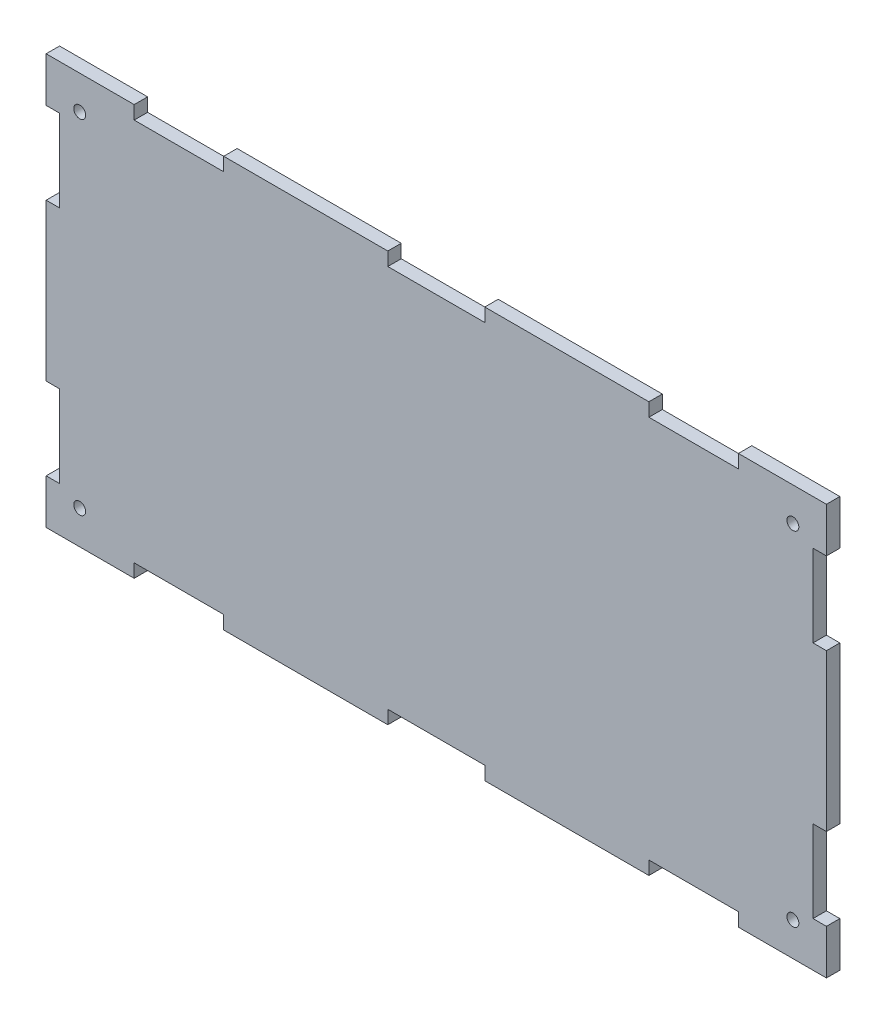
SolidWorks part; units mm, degrees
material "Бальса"
ref_plane "Спереди" through (0, 0, 0) normal (0, 0, 1) x (1, 0, 0)
ref_plane "Сверху" through (0, 0, 0) normal (0, 1, 0) x (1, 0, 0)
ref_plane "Справа" through (0, 0, 0) normal (1, 0, 0) x (0, 0, -1)
sketch "Эскиз1" plane through (0, 0, 0) normal (0, 0, 1) x (1, 0, 0)
  line L1 (0, 0) -> (209.2, 0)
  line L2 (0, 0) -> (0, 110)
  line L3 (0, 110) -> (209.2, 110)
  line L4 (209.2, 0) -> (209.2, 110)
  dimension "D1" = 110
  dimension "D2" = 209.2
base flange "Базовая кромка1" sketch "Эскиз1" thickness 3.6 reverse thickness direction no parameters "D1"=0.7366
sketch "Эскиз2" plane through (0, 0, 0) normal (0, 0, 1) x (1, 0, 0)
  line L0 (0, 55) -> (209.2, 55) construction
  line L1 (0, 0) -> (0, 110) construction
  line L2 (209.2, 0) -> (209.2, 110) construction
  line L3 (0, 110) -> (0, 0) construction
  line L4 (0, 34) -> (3.6, 34)
  line L5 (0, 34) -> (0, 12)
  line L6 (0, 12) -> (3.6, 12)
  line L7 (3.6, 34) -> (3.6, 12)
  line L8 (0, 0) -> (209.2, 0) construction
  line L9 (23.6, 0) -> (47.6, 0)
  line L10 (23.6, 0) -> (23.6, 3.6)
  line L11 (23.6, 3.6) -> (47.6, 3.6)
  line L12 (47.6, 0) -> (47.6, 3.6)
  line L13 (205.6, 76) -> (205.6, 98)
  line L14 (91.6, 0) -> (117.6, 0)
  line L15 (91.6, 0) -> (91.6, 3.6)
  line L16 (91.6, 3.6) -> (117.6, 3.6)
  line L17 (117.6, 0) -> (117.6, 3.6)
  line L18 (161.6, 0) -> (185.6, 0)
  line L19 (161.6, 0) -> (161.6, 3.6)
  line L20 (161.6, 3.6) -> (185.6, 3.6)
  line L21 (185.6, 0) -> (185.6, 3.6)
  line L22 (209.2, 34) -> (205.6, 34)
  line L23 (209.2, 34) -> (209.2, 12)
  line L24 (209.2, 12) -> (205.6, 12)
  line L25 (205.6, 34) -> (205.6, 12)
  line L26 (209.2, 98) -> (205.6, 98)
  line L27 (209.2, 76) -> (209.2, 98)
  line L28 (209.2, 76) -> (205.6, 76)
  line L29 (185.6, 110) -> (185.6, 106.4)
  line L30 (161.6, 106.4) -> (185.6, 106.4)
  line L31 (161.6, 110) -> (161.6, 106.4)
  line L32 (161.6, 110) -> (185.6, 110)
  line L33 (117.6, 110) -> (117.6, 106.4)
  line L34 (91.6, 106.4) -> (117.6, 106.4)
  line L35 (91.6, 110) -> (91.6, 106.4)
  line L36 (91.6, 110) -> (117.6, 110)
  line L37 (47.6, 110) -> (47.6, 106.4)
  line L38 (23.6, 106.4) -> (47.6, 106.4)
  line L39 (23.6, 110) -> (23.6, 106.4)
  line L40 (23.6, 110) -> (47.6, 110)
  line L41 (3.6, 76) -> (3.6, 98)
  line L42 (0, 98) -> (3.6, 98)
  line L43 (0, 76) -> (0, 98)
  line L44 (0, 76) -> (3.6, 76)
  point P30 (47.6, 1.8)
  dimension "D1" = 12
  dimension "D2" = 22
  dimension "D3" = 3.6
  dimension "D4" = 12
  dimension "D5" = 22
  dimension "D6" = 3.6
  dimension "D7" = 23.6
  dimension "D8" = 24
  dimension "D9" = 44
  dimension "D10" = 26
  dimension "D11" = 44
  dimension "D12" = 24
  dimension "D13" = 3.6
extrude "Вырез-Вытянуть1" cut sketch "Эскиз2" against normal up to next normal cut yes
sketch "Эскиз3" plane through (0, 0, -3.6) normal (0, 0, -1) x (-1, 0, 0)
  line L0 (-9, 101) -> (-9, 9) construction
  line L1 (-9, 9) -> (-200.2, 9) construction
  line L2 (-200.2, 9) -> (-200.2, 101) construction
  line L3 (-200.2, 101) -> (-9, 101) construction
  line L4 (0, 76) -> (0, 34) construction
  line L5 (-161.6, 110) -> (-117.6, 110) construction
  line L6 (-47.6, 0) -> (-91.6, 0) construction
  line L7 (-209.2, 34) -> (-209.2, 76) construction
  circle A0 centre (-9, 9) radius 1.6
  circle A1 centre (-9, 101) radius 1.6
  circle A2 centre (-200.2, 9) radius 1.6
  circle A3 centre (-200.2, 101) radius 1.6
  dimension "D5" = 3.2
  dimension "D1" = 9
  dimension "D2" = 9
  dimension "D3" = 9
  dimension "D4" = 9
extrude "Вырез-Вытянуть2" cut sketch "Эскиз3" against normal up to next normal cut yes
sketch "Сгиб-Линии1" [suppressed] plane through (0, 0, 0) normal (0, 1, 0) x (1, 0, 0)
sketch "Граничная рамка1" [suppressed] plane through (0, 0, 0) normal (0, 1, 0) x (1, 0, 0)
sheet metal parameters "Листовой металл3" thickness 3.6 parameters "D1"=0.7366
flat pattern "Развертка3" [suppressed]
sketch "Сгиб-Линии2" plane through (0, 0, 0) normal (0, 1, 0) x (1, 0, 0)
sketch3d "Граничная рамка2" [suppressed]
  line L0 (0, 0, 0) -> (209.2, 0, 0) construction
  line L1 (0, 58, 0) -> (209.2, 58, 0) construction
  line L2 (0, 0, 0) -> (0, 58, 0) construction
  line L3 (209.2, 0, 0) -> (209.2, 58, 0) construction
sheet metal parameters "Листовой металл4" thickness 3.6 parameters "D1"=0.7366
flat pattern "Развертка3"
sketch "Сгиб-Линии2" plane through (0, 0, 0) normal (0, 1, 0) x (1, 0, 0)
sketch3d "Граничная рамка2" [suppressed]
  line L0 (0, 0, 0) -> (209.2, 0, 0) construction
  line L1 (0, 58, 0) -> (209.2, 58, 0) construction
  line L2 (0, 0, 0) -> (0, 58, 0) construction
  line L3 (209.2, 0, 0) -> (209.2, 58, 0) construction
sheet metal parameters "Листовой металл5" thickness 3.6 parameters "D1"=0.7366
flat pattern "Развертка3"
sketch "Сгиб-Линии2" plane through (0, 0, 0) normal (0, 1, 0) x (1, 0, 0)
sketch3d "Граничная рамка2" [suppressed]
  line L0 (0, 0, 0) -> (209.2, 0, 0) construction
  line L1 (0, 58, 0) -> (209.2, 58, 0) construction
  line L2 (0, 0, 0) -> (0, 58, 0) construction
  line L3 (209.2, 0, 0) -> (209.2, 58, 0) construction
